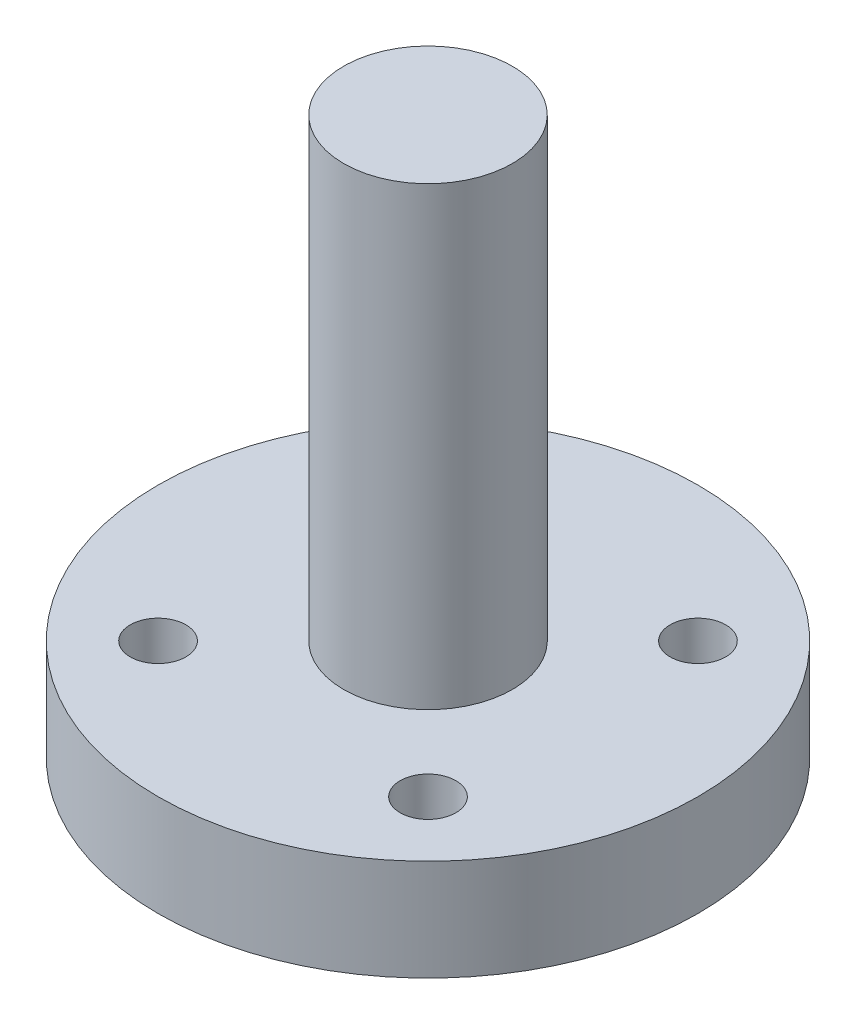
SolidWorks part; units mm, degrees
material "6061 Alloy"
ref_plane "Front Plane" through (0, 0, 0) normal (0, 0, 1) x (1, 0, 0)
ref_plane "Top Plane" through (0, 0, 0) normal (0, 1, 0) x (1, 0, 0)
ref_plane "Right Plane" through (0, 0, 0) normal (1, 0, 0) x (0, 0, -1)
sketch "Sketch1" plane through (0, 0, 0) normal (0, 1, 0) x (1, 0, 0)
  circle A0 centre (0, 0) radius 16
  dimension "D1" = 32
extrude "Boss-Extrude1" add sketch "Sketch1" along normal blind 6
sketch "Sketch3" plane through (0, 6, 0) normal (0, 1, 0) x (1, 0, 0)
  circle A1 centre (0, 0) radius 5
  dimension "D2" = 10
sketch "Sketch4" plane through (0, 0, 0) normal (0, -1, 0) x (1, 0, 0)
  line L1 (8, 8) -> (-8, 8) construction
  line L2 (8, 8) -> (8, -8) construction
  line L3 (8, -8) -> (-8, -8) construction
  line L4 (-8, 8) -> (-8, -8) construction
  line L5 (8, 8) -> (-8, -8) construction
  line L6 (8, -8) -> (-8, 8) construction
  point P0 (0, 0)
  dimension "D1" = 16
  dimension "D2" = 90
hole_wizard "Tap Drill for M4x0.7 Tap1" positions "Sketch5" profile "Sketch6" hole size "M4x0.7" standard "ANSI Metric" end condition through all
sketch "Sketch5" plane through (0, 0, 0) normal (0, -1, 0) x (-1, 0, 0)
  point P0 (-8, 8)
  point P3 (-8, -8)
  point P6 (8, -8)
  point P9 (8, 8)
sketch "Sketch6" plane through (8, 0, -8) normal (1, 0, 0) x (0, 0, -1)
  line L0 (0, 0) -> (0, 6)
  line L1 (0, 6) -> (1.65, 6)
  line L2 (1.65, 6) -> (1.65, 0)
  line L5 (1.65, 0) -> (0, 0)
  line L11 (0, -6.35) -> (0, 107.95) construction
  dimension "Thru Hole Dia." = 3.3
  dimension "Thru Hole Depth" = 6
extrude "Boss-Extrude2" add sketch "Sketch3" along normal blind 27
